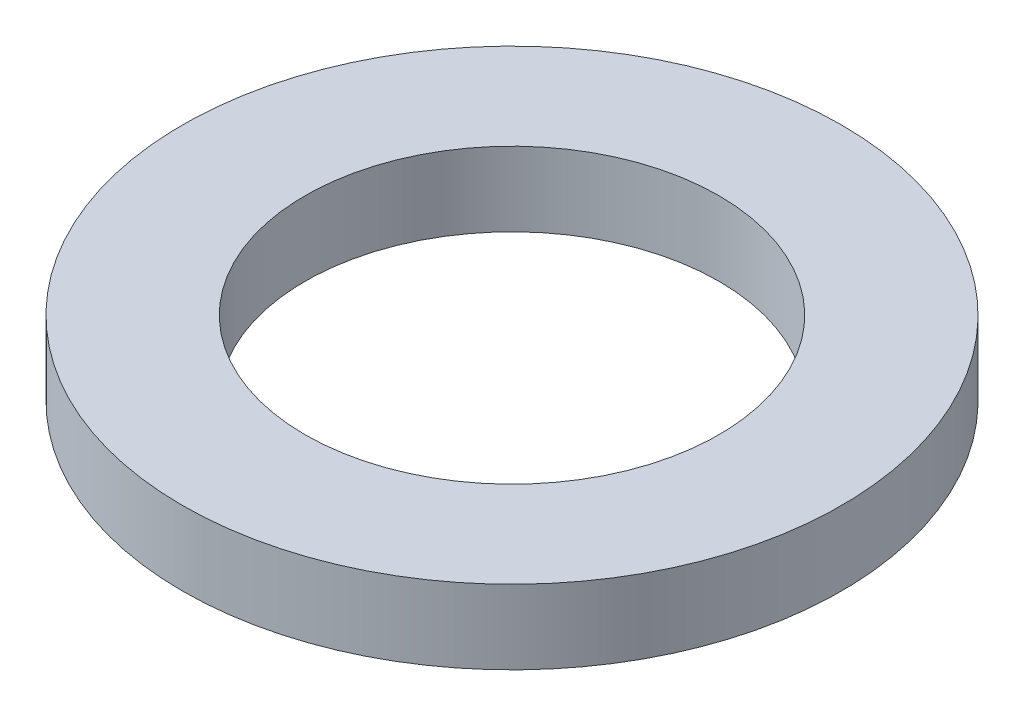
SolidWorks part; units mm, degrees
material "PTFE (general)"
ref_plane "Front Plane" through (0, 0, 0) normal (0, 0, 1) x (1, 0, 0)
ref_plane "Top Plane" through (0, 0, 0) normal (0, 1, 0) x (1, 0, 0)
ref_plane "Right Plane" through (0, 0, 0) normal (1, 0, 0) x (0, 0, -1)
sketch "Sketch1" plane through (0, 0, 0) normal (0, 0, 1) x (1, 0, 0)
  line L0 (0, 0) -> (0, -5.3675) construction
  line L1 (5.025, 0) -> (8, 0)
  line L2 (8, 0) -> (8, -1.8)
  line L3 (8, -1.8) -> (5.9, -1.8)
  line L4 (5.9, -1.8) -> (5.9, -2)
  line L5 (5.9, -2) -> (5.5, -2)
  line L6 (5.5, -2) -> (5.5, -1.8)
  line L7 (5.5, -1.8) -> (5.025, -1.8)
  line L8 (5.025, -1.8) -> (5.025, 0)
  point P3 (5.1, -4.5471)
  point P12 (0, -5.3675)
  dimension "D1" = 10.05
  dimension "D2" = 1.8
  dimension "D3" = 0.2
  dimension "D4" = 16
  dimension "D5" = 0.4
  dimension "D6" = 11
revolve "Revolve1" add sketch "Sketch1" angle 360 about L0
